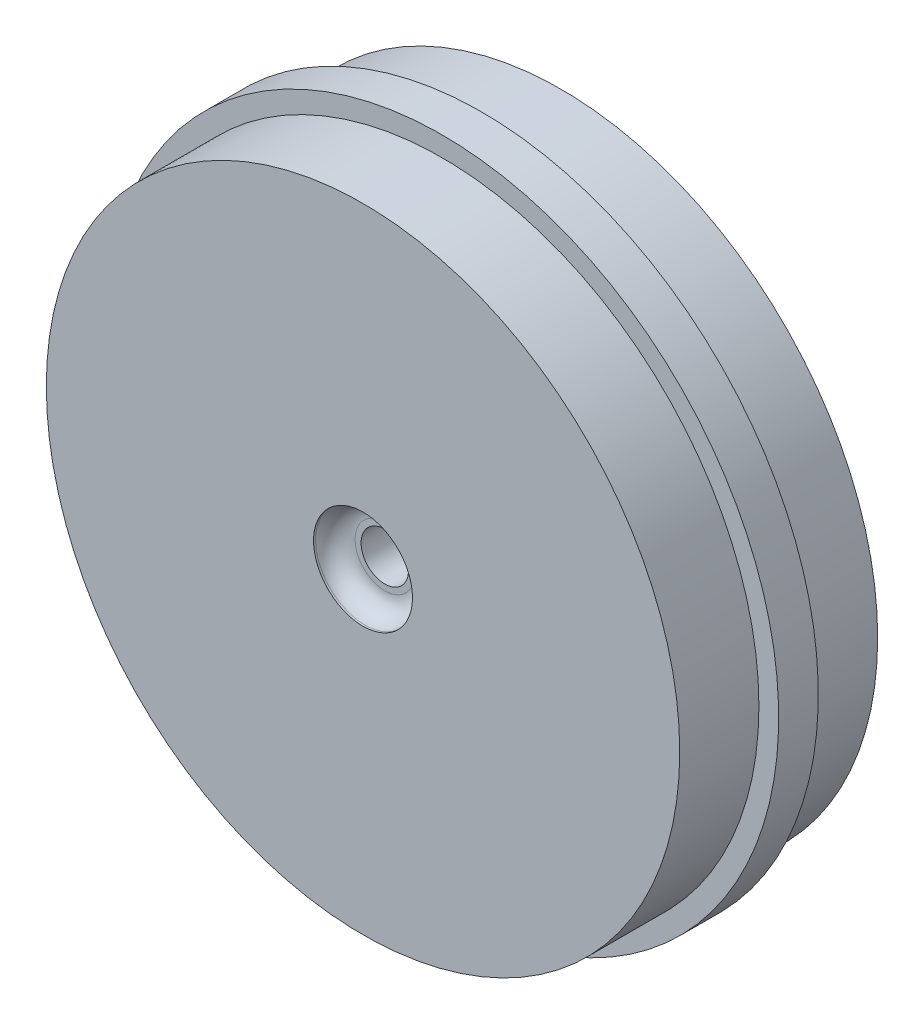
SolidWorks part; units mm, degrees
material "PET"
ref_plane "Plan de face" through (0, 0, 0) normal (0, 0, 1) x (1, 0, 0)
ref_plane "Plan de dessus" through (0, 0, 0) normal (0, 1, 0) x (1, 0, 0)
ref_plane "Plan de droite" through (0, 0, 0) normal (1, 0, 0) x (0, 0, -1)
sketch "Esquisse1" plane through (0, 0, 0) normal (0, 0, 1) x (1, 0, 0)
  circle A0 centre (0, 0) radius 14.5
  dimension "D1" = 29
extrude "Boss.-Extru.1" add sketch "Esquisse1" along normal blind 10
sketch "Esquisse2" plane through (0, 0, 0) normal (0, 0, 1) x (1, 0, 0)
  circle A0 centre (0, 0) radius 16.5
  dimension "D1" = 33
extrude "Boss.-Extru.2" add sketch "Esquisse2" along normal offset from surface (8 mm away) 1 from offset 1 up to face at (14.5, 0, 10)
sketch "Esquisse6" plane through (0, 0, 10) normal (0, 0, 1) x (1, 0, 0)
  circle A0 centre (0, 0) radius 13.5
  dimension "D1" = 27
extrude "Enlèv. mat.-Extru.4" cut sketch "Esquisse6" against normal blind 1
hole_wizard "Chambrage pour vis à tête ronde bombée M21" positions "Esquisse9" profile "Esquisse8" counterbore size "M2" standard "Ansi Metric" end condition through all
sketch "Esquisse9" plane through (0, 0, 9) normal (0, 0, 1) x (1, 0, 0)
  point P0 (0, 0)
sketch "Esquisse8" plane through (0, 0, 9) normal (1, 0, 0) x (0, -1, 0)
  line L0 (0, 0) -> (0, 9)
  line L1 (0, 9) -> (1.2, 9)
  line L3 (1.2, 9) -> (1.2, 1.6)
  line L4 (1.2, 1.6) -> (2.5, 1.6)
  line L5 (2.5, 1.6) -> (2.5, 0)
  line L7 (2.5, 0) -> (0, 0)
  line L11 (0, -6.35) -> (0, 107.95) construction
  dimension "Diamètre du perçage jusqu'au prochain" = 2.4
  dimension "Profondeur du perçage jusqu'au prochain" = 9
  dimension "Diamètre du chambrage" = 5
  dimension "Profondeur du chambrage" = 1.6
sketch "Esquisse13" plane through (0, 0, 0) normal (0, 0, -1) x (-1, 0, 0)
  circle A0 centre (0, 0) radius 13.5
  circle A1 centre (0, 0) radius 4.2
  dimension "D1" = 27
  dimension "D2" = 8.4
extrude "Enlèv. mat.-Extru.7" cut sketch "Esquisse13" against normal offset from surface (7 mm away) 2 up to face at (2.5, 0, 9)
sketch "Esquisse15" plane through (0, 0, 0) normal (0, 0, -1) x (-1, 0, 0)
  line L0 (-2.15, 2.0922) -> (-2.15, -2.0922)
  line L1 (2.15, 2.0922) -> (2.15, -2.0922)
  arc A0 (-2.15, -2.0922) -> (2.15, -2.0922) centre (0, 0) ccw
  arc A1 (2.15, 2.0922) -> (-2.15, 2.0922) centre (0, 0) ccw
  dimension "D1" = 6
  dimension "D2" = 2.15
  dimension "D3" = 2.15
extrude "Enlèv. mat.-Extru.8" cut sketch "Esquisse15" against normal blind 7
sketch "Sketch2" plane through (0, 0, 1) normal (0, 0, -1) x (-1, 0, 0)
  circle A0 centre (0, 0) radius 16.5
  circle A1 centre (0, 0) radius 14.5
extrude "Boss-Extrude2" add sketch "Sketch2" along normal up to surface (1 mm away) and the other way up to surface (9 mm away) up to face at (0, 0, 0) other way up to face at (13.5, 0, 10)
sketch "Sketch3" plane through (0, 0, 0) normal (0, 0, -1) x (-1, 0, 0)
  circle A0 centre (0, 0) radius 16.5
  circle A1 centre (0, 0) radius 22.5
  dimension "D1" = 6
extrude "Boss-Extrude3" add sketch "Sketch3" against normal up to surface (10 mm away) up to face at (13.5, 0, 10)
fillet "Fillet1" radius 1 2 edges at (-22.5, 0, 0) (22.5, 0, 10)
ref_plane "Plane1" through (0, 0, 0) normal (1, 0, 0) x (0, 0, -1)
sketch "Sketch4" plane through (0, 0, 0) normal (1, 0, 0) x (0, 0, -1)
  line L0 (-9, 22.5) -> (-1, 22.5) construction
  line L1 (-1, 22.5) -> (-9, 22.5) construction
  line L2 (-9, 22.5) -> (-9, 18)
  line L3 (-5, 22.5) -> (-5, 24.473) construction
  line L4 (-9, 18) -> (-1, 18)
  line L5 (-1, 18) -> (-1, 22.5)
  arc A0 (-9, 22.5) -> (-1, 22.5) centre (-5, 14.0611) cw
  point P10 (-5, 23.4)
  dimension "D2" = 0.9
extrude "Boss-Extrude4" add sketch "Sketch4" along normal blind 0.5 and the other way blind 0.5
pattern_circular "CirPattern1" count 70 over 360 about axis through (0, 0, 73.6396) along (0, 0, -1) of "Boss-Extrude4"
sketch "Sketch5" plane through (0, 0, 0) normal (0, 0, -1) x (-1, 0, 0)
  circle A0 centre (0, 0) radius 16
  circle A1 centre (0, 0) radius 40
  dimension "D1" = 32
  dimension "D2" = 80
extrude "Cut-Extrude1" cut sketch "Sketch5" against normal blind 20
sketch "Sketch6" plane through (0, 0, 0) normal (0, 0, -1) x (-1, 0, 0)
  circle A0 centre (0, 0) radius 16
  circle A1 centre (0, 0) radius 17
  circle A2 centre (0, 0) radius 16 construction
  dimension "D1" = 1
extrude "Boss-Extrude5" add sketch "Sketch6" against normal blind 2 from offset 4 offset against normal yes
sketch "Sketch8" plane through (0, 0, 9) normal (0, 0, 1) x (1, 0, 0)
  circle A0 centre (0, 0) radius 13.5
  circle A1 centre (0, 0) radius 2.5
  circle A2 centre (0, 0) radius 13.5 construction
  circle A3 centre (0, 0) radius 2.5 construction
extrude "Boss-Extrude6" add sketch "Sketch8" along normal up to surface (1 mm away) up to face at (13.5, 0, 10)
sketch "Sketch9" plane through (0, 0, 7.4) normal (0, 0, 1) x (1, 0, 0)
  circle A0 centre (0, 0) radius 2.5
  circle A1 centre (0, 0) radius 1.2
  circle A2 centre (0, 0) radius 1.2 construction
  circle A3 centre (0, 0) radius 2.5 construction
extrude "Boss-Extrude7" add sketch "Sketch9" along normal blind 1.5
fillet "Fillet2" radius 1 1 edges at (2.5, 0, 8.9)
